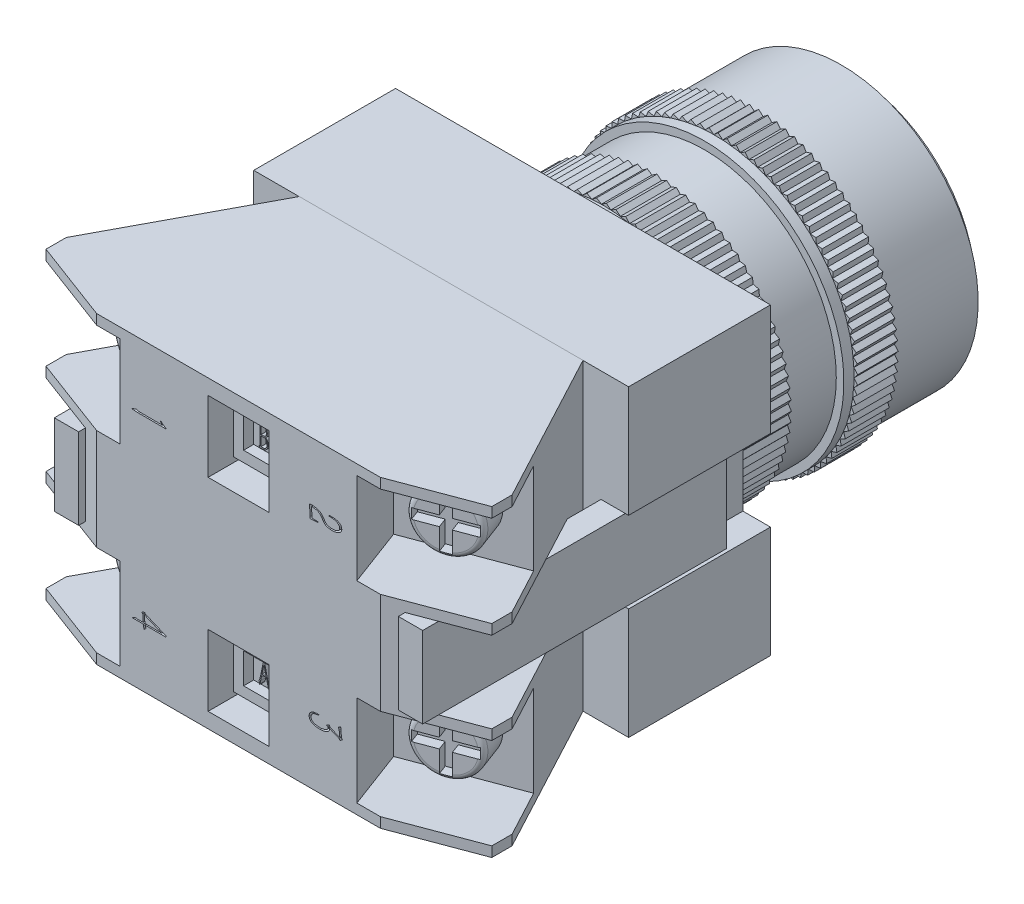
SolidWorks part; units mm, degrees
ref_plane "前视基准面" through (0, 0, 0) normal (0, 0, 1) x (1, 0, 0)
ref_plane "上视基准面" through (0, 0, 0) normal (0, 1, 0) x (1, 0, 0)
ref_plane "右视基准面" through (0, 0, 0) normal (1, 0, 0) x (0, 0, -1)
sketch "草图1" plane through (0, 0, 0) normal (0, 1, 0) x (1, 0, 0)
  line L0 (-14, 0) -> (-22, -15)
  line L1 (-55, 0) -> (55, 0) construction
  line L2 (-22, -15) -> (-22, -17)
  line L3 (-22, -17) -> (-14, -20)
  line L4 (-14, -20) -> (0, -20)
  line L5 (0, -55) -> (0, 55) construction
  line L6 (0, -20) -> (0, 0)
  line L7 (0, 0) -> (-14, 0)
  dimension "D1" = 8
  dimension "D2" = 14
  dimension "D3" = 8
  dimension "D4" = 5
  dimension "D5" = 3
  dimension "D6" = 20
  dimension "D7" = 14
extrude "凸台-拉伸1" add sketch "草图1" along normal blind 30
mirror "镜向1" of "凸台-拉伸1"
sketch "草图2" plane through (0, 0, 0) normal (0, 0, -1) x (-1, 0, 0)
  line L0 (0, 55) -> (0, -55) construction
  line L1 (-18.5, 30) -> (18.5, 30)
  line L2 (-18.5, 30) -> (-18.5, 0)
  line L3 (-18.5, 0) -> (18.5, 0)
  line L4 (18.5, 30) -> (18.5, 0)
  line L5 (-18.5, 30) -> (18.5, 0) construction
  line L6 (-18.5, 0) -> (18.5, 30) construction
  line L7 (14, 0) -> (22, 0) construction
  point P0 (0, 15)
  dimension "D1" = 30
  dimension "D2" = 37
extrude "凸台-拉伸2" add sketch "草图2" along normal blind 14
sketch "草图4" plane through (0, 0, -14) normal (0, 0, -1) x (-1, 0, 0)
  line L0 (-18.5, 15) -> (27.3157, 15) construction
  line L1 (-18.5, 30) -> (-18.5, 0) construction
  line L2 (15.7778, 19) -> (15.7778, 11)
  line L3 (15.7778, 11) -> (27.3157, 11)
  line L4 (27.3157, 11) -> (27.3157, 19)
  line L5 (27.3157, 19) -> (15.7778, 19)
  dimension "D1" = 4
  dimension "D2" = 4
extrude "切除-拉伸1" cut sketch "草图4" against normal through all
mirror "镜向2" about plane through (0, 0, 0) normal (1, 0, 0) of "切除-拉伸1"
sketch "草图30" plane through (0, 30, 0) normal (0, 1, 0) x (1, 0, 0)
  line L1 (-18.5, 14) -> (18.5, 14)
  line L2 (-18.5, 14) -> (-18.5, 0)
  line L3 (-18.5, 0) -> (18.5, 0)
  line L4 (18.5, 14) -> (18.5, 0)
extrude "切除-拉伸8" cut sketch "草图30" against normal blind 0.01
sketch "草图31" plane through (0, 0, 0) normal (0, -1, 0) x (1, 0, 0)
  line L1 (-18.5, 0) -> (18.5, 0)
  line L2 (-18.5, 0) -> (-18.5, -14)
  line L3 (-18.5, -14) -> (18.5, -14)
  line L4 (18.5, 0) -> (18.5, -14)
extrude "切除-拉伸9" cut sketch "草图31" against normal blind 0.01
sketch "草图9" plane through (0, 0, 20) normal (0, 0, 1) x (1, 0, 0)
  line L0 (22, 11) -> (15.7778, 11) construction
  line L1 (15.7778, 19) -> (18.1778, 19)
  line L2 (15.7778, 19) -> (15.7778, 11)
  line L3 (15.7778, 11) -> (18.1778, 11)
  line L4 (18.1778, 19) -> (18.1778, 11)
  dimension "D1" = 2.4
extrude "凸台-拉伸9" add sketch "草图9" against normal blind 30
mirror "镜向6" about plane through (0, 0, 0) normal (1, 0, 0) of bodies 116
sketch "草图16" plane through (0, 0, 20) normal (0, 0, 1) x (1, 0, 0)
  line L0 (0, -16.5001) -> (0, 16.5001) construction
  line L1 (-3, 28.5) -> (3, 28.5)
  line L2 (-3, 28.5) -> (-3, 21.5)
  line L3 (-3, 21.5) -> (3, 21.5)
  line L4 (3, 28.5) -> (3, 21.5)
  line L5 (-3, 28.5) -> (3, 21.5) construction
  line L6 (-3, 21.5) -> (3, 28.5) construction
  line L7 (-14, 30) -> (14, 30) construction
  line L8 (-3, 8.5) -> (3, 8.5)
  line L9 (-3, 8.5) -> (-3, 1.5)
  line L10 (-3, 1.5) -> (3, 1.5)
  line L11 (3, 8.5) -> (3, 1.5)
  line L12 (-3, 8.5) -> (3, 1.5) construction
  line L13 (-3, 1.5) -> (3, 8.5) construction
  line L14 (-14, 0) -> (14, 0) construction
  point P0 (0, 25)
  point P7 (0, 5)
  dimension "D1" = 6
  dimension "D2" = 7
  dimension "D3" = 1.5
  dimension "D4" = 6
  dimension "D5" = 7
  dimension "D6" = 1.5
extrude "切除-拉伸6" cut sketch "草图16" against normal blind 5
sketch "草图17" plane through (0, 0, 15) normal (0, 0, 1) x (1, 0, 0)
  line L0 (0, -16.5001) -> (0, 16.5001) construction
  line L1 (-2.5, 27.5061) -> (2.5, 27.5061)
  line L2 (-2.5, 27.5061) -> (-2.5, 22.5061)
  line L3 (-2.5, 22.5061) -> (2.5, 22.5061)
  line L4 (2.5, 27.5061) -> (2.5, 22.5061)
  line L5 (-2.5, 27.5061) -> (2.5, 22.5061) construction
  line L6 (-2.5, 22.5061) -> (2.5, 27.5061) construction
  line L8 (-2.5, 7.4282) -> (2.5, 7.4282)
  line L9 (-2.5, 7.4282) -> (-2.5, 2.4282)
  line L10 (-2.5, 2.4282) -> (2.5, 2.4282)
  line L11 (2.5, 7.4282) -> (2.5, 2.4282)
  line L12 (-2.5, 7.4282) -> (2.5, 2.4282) construction
  line L13 (-2.5, 2.4282) -> (2.5, 7.4282) construction
  point P0 (0, 25.0061)
  point P7 (0, 4.9282)
  dimension "D1" = 5
  dimension "D2" = 5
  dimension "D3" = 5
  dimension "D4" = 5
extrude "凸台-拉伸12" add sketch "草图17" along normal blind 3
sketch "草图32" plane through (0, 0, 18) normal (0, 0, 1) x (1, 0, 0)
  line L0 (0, -16.5001) -> (0, 16.5001) construction
  line L1 (-1.5, 26.5643) -> (1.5, 26.5643)
  line L2 (-1.5, 26.5643) -> (-1.5, 23.5643)
  line L3 (-1.5, 23.5643) -> (1.5, 23.5643)
  line L4 (1.5, 26.5643) -> (1.5, 23.5643)
  line L5 (-1.5, 26.5643) -> (1.5, 23.5643) construction
  line L6 (-1.5, 23.5643) -> (1.5, 26.5643) construction
  line L8 (-1.5, 6.4282) -> (1.5, 6.4282)
  line L9 (-1.5, 6.4282) -> (-1.5, 3.4282)
  line L10 (-1.5, 3.4282) -> (1.5, 3.4282)
  line L11 (1.5, 6.4282) -> (1.5, 3.4282)
  line L12 (-1.5, 6.4282) -> (1.5, 3.4282) construction
  line L13 (-1.5, 3.4282) -> (1.5, 6.4282) construction
  point P0 (0, 25.0643)
  point P7 (0, 4.9282)
  dimension "D1" = 3
  dimension "D2" = 3
  dimension "D3" = 3
  dimension "D4" = 3
extrude "切除-拉伸10" cut sketch "草图32" against normal blind 1
sketch "草图33" plane through (0, 0, 17) normal (0, 0, 1) x (1, 0, 0)
  line L0 (-0.9736, 23.8769) -> (0.9613, 23.8769) construction
  line L1 (-0.9736, 3.7293) -> (1.0351, 3.7293) construction
  text T0 "B" font "汉仪长仿宋体" height in points 9
  text T1 "A" font "汉仪长仿宋体" height in points 9
extrude "凸台-拉伸22" add sketch "草图33" along normal blind 0.5
sketch "草图21" plane through (0, 0, -14) normal (0, 0, -1) x (-1, 0, 0)
  line L0 (0, 16.5001) -> (0, -16.5001) construction
  line L1 (15.7778, 19) -> (15.7778, 11) construction
  circle A0 centre (0, 15) radius 13.25
  point P6 (15.7778, 15)
  dimension "D1" = 26.5
extrude "凸台-拉伸13" add sketch "草图21" along normal blind 7
sketch "草图22" plane through (0, 0, -21) normal (0, 0, -1) x (-1, 0, 0)
  line L0 (-3.5763, 27.7017) -> (-3.1452, 28.2006)
  line L1 (-3.1452, 28.2006) -> (-2.5097, 27.9566)
  arc A1 (-3.5763, 27.7017) -> (-2.5097, 27.9566) centre (-3.043, 27.8291) ccw
extrude "凸台-拉伸15" add sketch "草图22" against normal blind 5
pattern_circular "阵列(圆周)1" count 89 over 360 about axis through (0, 15, -21) along (0, 0, -1) of "凸台-拉伸13", "凸台-拉伸15"
sketch "草图23" plane through (0, 0, -21) normal (0, 0, -1) x (-1, 0, 0)
  circle A0 centre (0, 15) radius 13
  dimension "D1" = 26
extrude "凸台-拉伸16" add sketch "草图23" along normal blind 5
sketch "草图24" plane through (0, 0, -26) normal (0, 0, -1) x (-1, 0, 0)
  circle A0 centre (0, 15) radius 13.75
  dimension "D1" = 27.5
extrude "凸台-拉伸17" add sketch "草图24" along normal blind 5
sketch "草图25" plane through (0, 0, -31) normal (0, 0, -1) x (-1, 0, 0)
  line L0 (-1.6893, 28.6111) -> (-1.2331, 29.0655)
  line L1 (-1.2331, 29.0655) -> (-0.6948, 28.6661)
  arc A0 (-1.6893, 28.6111) -> (-0.6948, 28.6661) centre (-1.2598, 29.861) ccw
extrude "凸台-拉伸18" add sketch "草图25" against normal blind 4
pattern_circular "阵列(圆周)2" count 99 over 360 about axis through (0, 15, -31) along (0, 0, -1) of "凸台-拉伸18"
sketch "草图26" plane through (0, 0, -31) normal (0, 0, -1) x (-1, 0, 0)
  circle A0 centre (0, 15) radius 13.5
  dimension "D1" = 27
extrude "凸台-拉伸19" add sketch "草图26" along normal blind 8.5
sketch "草图27" plane through (0, 0, -39.5) normal (0, 0, -1) x (-1, 0, 0)
  circle A0 centre (0, 15) radius 12.5
  dimension "D1" = 25
extrude "切除-拉伸7" cut sketch "草图27" against normal blind 5
sketch "草图28" plane through (0, 0, -34.5) normal (0, 0, -1) x (-1, 0, 0)
  circle A0 centre (0, 15) radius 5
  dimension "D1" = 10
extrude "凸台-拉伸20" add sketch "草图28" along normal blind 5.5
sketch "草图29" plane through (0, 0, -40) normal (0, 0, -1) x (-1, 0, 0)
  circle A0 centre (0, 15) radius 12.25
  dimension "D1" = 24.5
extrude "凸台-拉伸21" add sketch "草图29" along normal blind 0.5
sketch "草图34" plane through (-8.3014, 0, 22.137) normal (-0.3511, 0, 0.9363) x (0.9363, 0, 0.3511)
  line L0 (-14.6301, 30) -> (-6.0861, 30) construction
  line L1 (-16.9176, 29) -> (-3.9176, 29)
  line L2 (-16.9176, 29) -> (-16.9176, 20)
  line L3 (-16.9176, 20) -> (-3.9176, 20)
  line L4 (-3.9176, 29) -> (-3.9176, 20)
  line L5 (-16.9176, 29) -> (-3.9176, 20) construction
  line L6 (-16.9176, 20) -> (-3.9176, 29) construction
  line L7 (-7.9848, 19) -> (-10.548, 19) construction
  point P0 (-10.4176, 24.5)
  dimension "D1" = 1
  dimension "D2" = 1
  dimension "D3" = 13
extrude "切除-拉伸11" cut sketch "草图34" against normal blind 7
sketch "草图35" plane through (-5.8435, 0, 15.5827) normal (-0.3511, 0, 0.9363) x (0.9363, 0, 0.3511)
  circle A0 centre (-9.2867, 24.5) radius 3
  dimension "D1" = 6
extrude "凸台-拉伸23" add sketch "草图35" along normal blind 3
ref_plane "基准面1" through (0, 15, 0) normal (0, -1, 0) x (-1, 0, 0)
mirror "镜向7" about plane through (0, 15, 0) normal (0, -1, 0) of "凸台-拉伸23", "切除-拉伸11"
mirror "镜向9" about plane through (0, 0, 0) normal (1, 0, 0) of "切除-拉伸11", "凸台-拉伸23", "镜向7"
sketch "草图37" plane through (0, 0, 20) normal (0, 0, 1) x (1, 0, 0)
  line L0 (6.684, 24.5) -> (6.684, 5.1723) construction
  line L1 (-10.684, 24.5) -> (-10.684, 5.1723) construction
  line L2 (-11.684, 29) -> (-11.684, 20) construction
  line L3 (11.684, 29) -> (11.684, 20) construction
  text T0 "23"
  text T1 "14"
  dimension "D1" = 1
  dimension "D2" = 5
extrude "切除-拉伸13" cut sketch "草图37" against normal blind 0.5
sketch "草图39" plane through (-5.8435, 0, 15.5827) normal (-0.3511, 0, 0.9363) x (0.9363, 0, 0.3511)
  point P0 (-9.2867, 24.5)
  point P1 (-9.2867, 5.5)
sketch "草图40" plane through (-6.8969, 0, 18.3917) normal (-0.3511, 0, 0.9363) x (0.9363, 0, 0.3511)
  line L0 (-9.7867, 24) -> (-9.7867, 21.8887)
  line L1 (-11.9276, 25) -> (-9.7867, 25)
  line L2 (-11.9276, 25) -> (-11.9276, 24)
  line L3 (-11.9276, 24) -> (-9.7867, 24)
  line L4 (-6.6459, 25) -> (-6.6459, 24)
  line L7 (-9.7867, 27.1113) -> (-8.7867, 27.1113)
  line L8 (-9.7867, 27.1113) -> (-9.7867, 25)
  line L9 (-9.7867, 21.8887) -> (-8.7867, 21.8887)
  line L10 (-8.7867, 27.1113) -> (-8.7867, 25)
  line L14 (-8.7867, 25) -> (-6.6459, 25)
  line L16 (-8.7867, 24) -> (-8.7867, 21.8887)
  line L18 (-8.7867, 24) -> (-6.6459, 24)
  point P0 (-9.2867, 24.5)
  point P6 (-9.2867, 24.5)
  dimension "D1" = 1
  dimension "D2" = 1
extrude "切除-拉伸14" cut sketch "草图40" against normal blind 1
mirror "镜向10" about plane through (0, 15, 0) normal (0, -1, 0) of "切除-拉伸14"
mirror "镜向11" about plane through (0, 0, 0) normal (1, 0, 0) of "镜向10"
sketch "草图41" plane through (5.8435, 0, 15.5827) normal (0.3511, 0, 0.9363) x (0.9363, 0, -0.3511)
  point P0 (9.2867, 24.5)
  point P1 (9.2867, 5.5)
fillet "圆角1" radius 0.5 4 edges at (-12.7833, 24.5, 16.1842) (-12.7833, 5.5, 16.1842) (12.7833, 24.5, 16.1842) (12.7833, 5.5, 16.1842)
sketch "0_0_Point" plane through (-5.8435, 0, 15.5827) normal (-0.3511, 0, 0.9363) x (0.9363, 0, 0.3511)
  point P0 (-9.2867, 24.5)
other "0_0" parameters "直径"=2, "端头长度"=2
ref_axis "基准轴1" through (-18.0502, 24.5, 21.6852) along (0.3511, 0, -0.9363)
sketch "0_1_Point" plane through (5.8435, 0, 15.5827) normal (0.3511, 0, 0.9363) x (0.9363, 0, -0.3511)
  point P0 (9.2867, 24.5)
other "0_1" parameters "直径"=2, "端头长度"=2
ref_axis "基准轴2" through (18.0502, 24.5, 21.6852) along (-0.3511, 0, -0.9363)
sketch "1_0_Point" plane through (5.8435, 0, 15.5827) normal (0.3511, 0, 0.9363) x (0.9363, 0, -0.3511)
  point P0 (9.2867, 5.5)
other "1_0" parameters "直径"=2, "端头长度"=2
ref_axis "基准轴3" through (18.0502, 5.5, 21.6852) along (-0.3511, 0, -0.9363)
sketch "1_1_Point" plane through (-5.8435, 0, 15.5827) normal (-0.3511, 0, 0.9363) x (0.9363, 0, 0.3511)
  point P0 (-9.2867, 5.5)
other "1_1" parameters "直径"=2, "端头长度"=2
ref_axis "基准轴4" through (-18.0502, 5.5, 21.6852) along (0.3511, 0, -0.9363)
